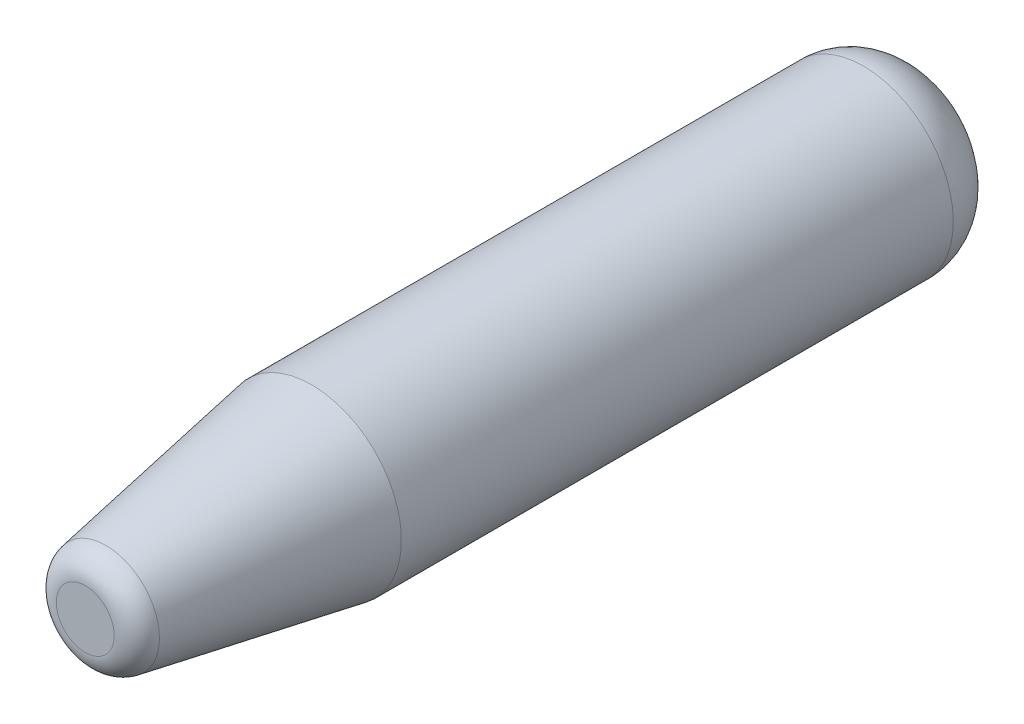
SolidWorks part; units mm, degrees
ref_plane "Front Plane" through (0, 0, 0) normal (0, 0, 1) x (1, 0, 0)
ref_plane "Top Plane" through (0, 0, 0) normal (0, 1, 0) x (1, 0, 0)
ref_plane "Right Plane" through (0, 0, 0) normal (1, 0, 0) x (0, 0, -1)
sketch "Sketch1" plane through (0, 0, 0) normal (0, 0, 1) x (1, 0, 0)
  circle A0 centre (0, 0) radius 228.6
extrude "Boss-Extrude1" add sketch "Sketch1" along normal blind 2133.6
ref_axis "Axis1" through (0, 0, 2133.6) along (0, 0, -1)
fillet "Fillet1" radius 152.4 1 edges at (228.6, 0, 0)
chamfer "Chamfer1" distance 101.6 angle 80 1 edges at (228.6, 0, 2133.6) first distance on face at (228.6, 0, 2133.6)
fillet "Fillet2" radius 63.5 1 edges at (127, 0, 2133.6)
